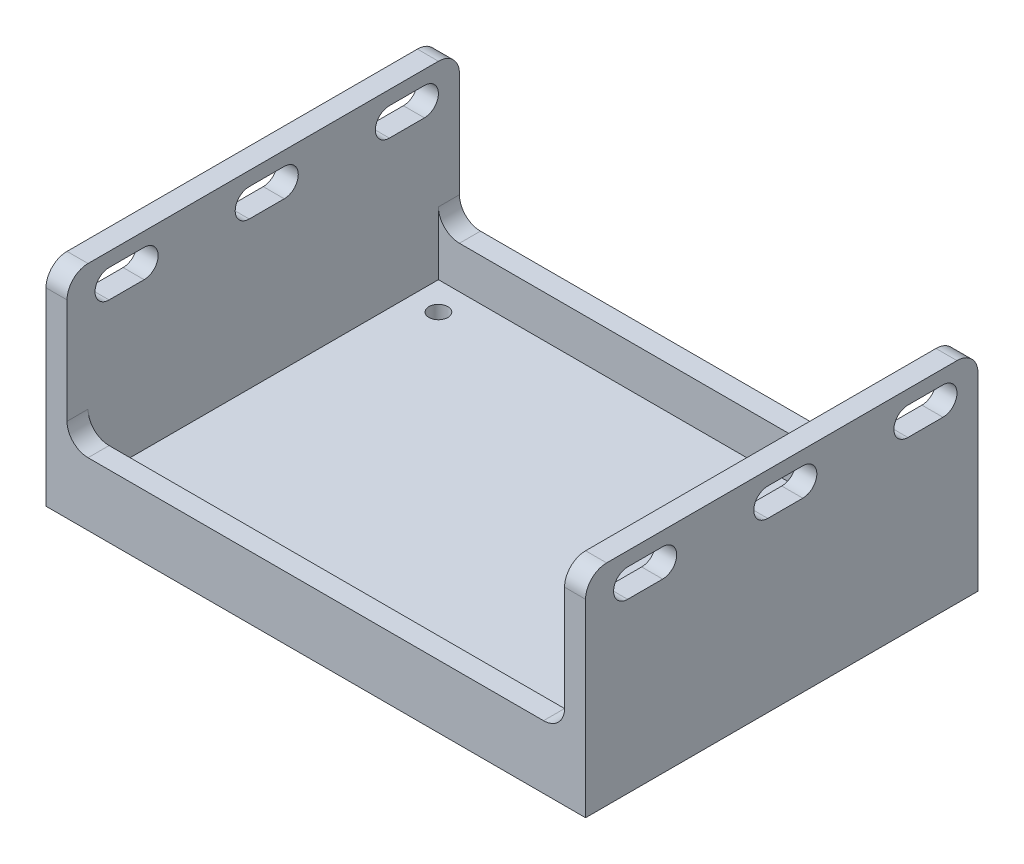
SolidWorks part; units mm, degrees
ref_plane "Front Plane" through (0, 0, 0) normal (0, 0, 1) x (1, 0, 0)
ref_plane "Top Plane" through (0, 0, 0) normal (0, 1, 0) x (1, 0, 0)
ref_plane "Right Plane" through (0, 0, 0) normal (1, 0, 0) x (0, 0, -1)
sketch "Sketch1" plane through (0, 0, 0) normal (0, 1, 0) x (1, 0, 0)
  line L1 (35.5, 25) -> (-35.5, 25)
  line L2 (35.5, 25) -> (35.5, -25)
  line L3 (35.5, -25) -> (-35.5, -25)
  line L4 (-35.5, 25) -> (-35.5, -25)
  line L5 (0, -25) -> (0, 25) construction
  line L6 (35.5, 0) -> (-35.5, 0) construction
  line L7 (31.5, 21) -> (-31.5, 21) construction
  line L8 (31.5, 21) -> (31.5, -21) construction
  line L9 (31.5, -21) -> (-31.5, -21) construction
  line L10 (-31.5, 21) -> (-31.5, -21) construction
  line L11 (0, -21) -> (0, 21) construction
  line L12 (31.5, 0) -> (-31.5, 0) construction
  circle A0 centre (-31.5, 21) radius 1.35
  circle A1 centre (31.5, 21) radius 1.35
  circle A2 centre (31.5, -21) radius 1.35
  circle A3 centre (-31.5, -21) radius 1.35
  point P0 (0, 0)
  point P4 (0, 0)
  dimension "D5" = 2.7
  dimension "D1" = 50
  dimension "D2" = 71
  dimension "D3" = 42
  dimension "D4" = 63
extrude "Boss-Extrude1" add sketch "Sketch1" along normal blind 3
sketch "Sketch2" plane through (0, 0, 0) normal (0, 1, 0) x (1, 0, 0)
  line L8 (-38.5, 28) -> (-38.5, -28)
  line L9 (-38.5, -28) -> (38.5, -28)
  line L10 (38.5, -28) -> (38.5, 28)
  line L11 (38.5, 28) -> (-38.5, 28)
  line L12 (-38.5, 28) -> (-38.5, -28)
  line L13 (-38.5, -28) -> (38.5, -28)
  line L14 (38.5, -28) -> (38.5, 28)
  line L15 (38.5, 28) -> (-38.5, 28)
  line L16 (-35.5, 25) -> (-35.5, -25)
  line L17 (-35.5, -25) -> (35.5, -25)
  line L18 (35.5, -25) -> (35.5, 25)
  line L19 (35.5, 25) -> (-35.5, 25)
  line L20 (-35.5, 25) -> (-35.5, -25)
  line L21 (-35.5, -25) -> (35.5, -25)
  line L22 (35.5, -25) -> (35.5, 25)
  line L23 (35.5, 25) -> (-35.5, 25)
  dimension "D1" = 3
  dimension "D2" = 0
extrude "Boss-Extrude2" add sketch "Sketch2" along normal blind 30
sketch "Sketch3" plane through (0, 0, -28) normal (0, 0, -1) x (-1, 0, 0)
  line L1 (-38.5, 30) -> (-38.5, 0) construction
  line L2 (-35.5, 39) -> (35.5, 39)
  line L3 (-35.5, 39) -> (-35.5, 9)
  line L4 (-35.5, 9) -> (35.5, 9)
  line L5 (35.5, 39) -> (35.5, 9)
  line L6 (38.5, 30) -> (38.5, 0) construction
  dimension "D1" = 9
  dimension "D2" = 3
  dimension "D3" = 3
  dimension "D4" = 30
extrude "Cut-Extrude1" cut sketch "Sketch3" against normal through all
sketch "Sketch4" plane through (-38.5, 0, 0) normal (-1, 0, 0) x (0, 0, 1)
  line L0 (-20.5, 26) -> (-20.5, 30) construction
  line L1 (-28, 30) -> (28, 30) construction
  line L2 (-18, 26) -> (-23, 26) construction
  line L3 (-18, 24) -> (-23, 24)
  line L4 (-18, 28) -> (-23, 28)
  line L5 (-23, 26) -> (-28, 26) construction
  line L6 (-28, 30) -> (-28, 0) construction
  line L7 (2, 28) -> (-3, 28)
  line L8 (2, 24) -> (-3, 24)
  line L9 (2, 26) -> (-3, 26) construction
  line L10 (22, 28) -> (17, 28)
  line L11 (22, 24) -> (17, 24)
  line L12 (22, 26) -> (17, 26) construction
  arc A0 (-18, 24) -> (-18, 28) centre (-18, 26) ccw
  arc A1 (-23, 28) -> (-23, 24) centre (-23, 26) ccw
  arc A2 (2, 24) -> (2, 28) centre (2, 26) ccw
  arc A3 (-3, 28) -> (-3, 24) centre (-3, 26) ccw
  arc A4 (22, 24) -> (22, 28) centre (22, 26) ccw
  arc A5 (17, 28) -> (17, 24) centre (17, 26) ccw
  point P7 (-20.5, 26)
  point P20 (-0.5, 26)
  point P27 (19.5, 26)
  dimension "D3" = 2
  dimension "D1" = 5
  dimension "D2" = 5
  dimension "D4" = 4
  dimension "D5" = 3
extrude "Cut-Extrude2" cut sketch "Sketch4" against normal through all
fillet "Fillet1" radius 3 8 edges at (-37, 30, 28) (-37, 30, -28) (37, 30, 28) (37, 30, -28) (-35.5, 9, -26.5) (-35.5, 9, 26.5) (35.5, 9, 26.5) (35.5, 9, -26.5)
